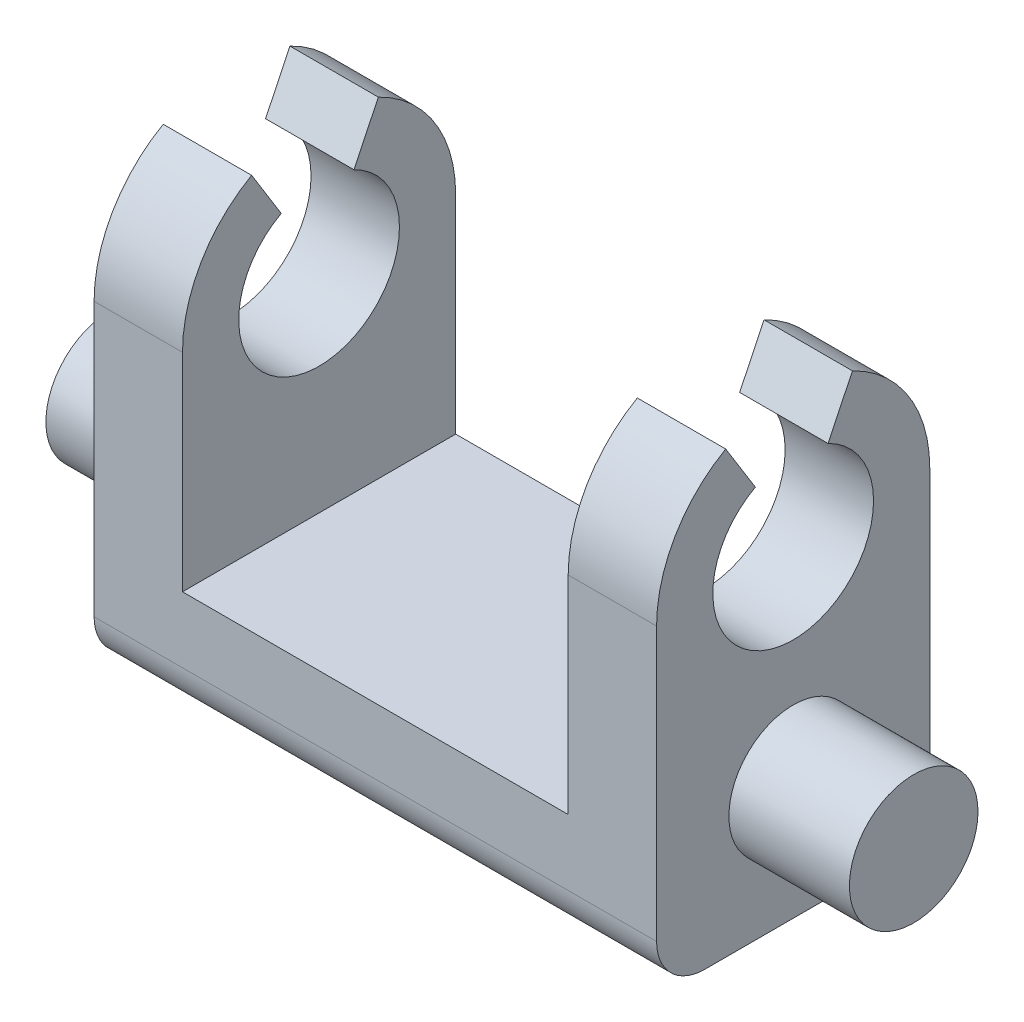
SolidWorks part; units mm, degrees
ref_plane "Front Plane" through (0, 0, 0) normal (0, 0, 1) x (1, 0, 0)
ref_plane "Top Plane" through (0, 0, 0) normal (0, 1, 0) x (1, 0, 0)
ref_plane "Right Plane" through (0, 0, 0) normal (1, 0, 0) x (0, 0, -1)
sketch "Sketch1" plane through (0, 0, 0) normal (1, 0, 0) x (0, 0, -1)
  circle A0 centre (0, 0) radius 8
  dimension "D1" = 16
extrude "Boss-Extrude1" add sketch "Sketch1" along normal mid plane 100
sketch "Sketch2" plane through (0, 0, 0) normal (1, 0, 0) x (0, 0, -1)
  line L0 (-11, -15) -> (11, -15)
  line L1 (17, -9) -> (17, 25)
  line L2 (-17, 25) -> (-17, -9)
  arc A0 (17, 25) -> (-17, 25) centre (0, 25) ccw
  circle A1 centre (0, 25) radius 10
  arc A2 (11, -15) -> (17, -9) centre (11, -9) ccw
  arc A3 (-11, -15) -> (-17, -9) centre (-11, -9) cw
  point P5 (0, -15)
  dimension "D3" = 20
  dimension "D4" = 17
  dimension "D5" = 6
  dimension "D1" = 15
  dimension "D2" = 40
extrude "Boss-Extrude2" add sketch "Sketch2" along normal mid plane 70
ref_axis "Axis1" through (-55, 0, 0) along (1, 0, 0)
sketch "Sketch3" plane through (0, 0, 0) normal (0, 0, 1) x (1, 0, 0)
  line L0 (-24, 42) -> (-24, -0.81)
  line L1 (35, 42) -> (-35, 42) construction
  line L3 (-24, -0.81) -> (24, -0.81)
  line L4 (24, -0.81) -> (24, 42)
  line L5 (24, 42) -> (-24, 42)
  point P4 (0, -0.81)
  dimension "D1" = 48
  dimension "D2" = 42.81
extrude "Cut-Extrude1" cut sketch "Sketch3" against normal through all both and the other way through all
sketch "Sketch4" plane through (35, 0, 0) normal (1, 0, 0) x (0, 0, -1)
  line L0 (-8.3982, 39.7807) -> (-4.7062, 33.8234)
  line L1 (7.3751, 40.3169) -> (4.3383, 34.0099)
  circle A0 centre (0, 25) radius 10 construction
  arc A1 (17, 25) -> (-17, 25) centre (0, 25) ccw construction
  arc A2 (4.3383, 34.0099) -> (-4.7062, 33.8234) centre (0, 25) ccw
  arc A3 (7.3751, 40.3169) -> (-8.3982, 39.7807) centre (0, 25) ccw
extrude "Cut-Extrude2" cut sketch "Sketch4" against normal up to surface (70 mm away) up to face at (-35, 0, -8)
